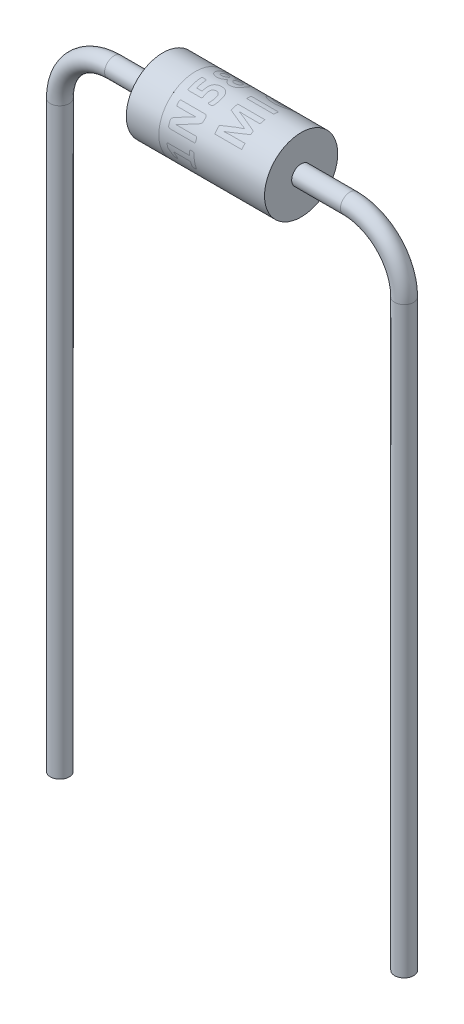
SolidWorks part; units mm, degrees
other "Diode"
other "Cathode Silver Band"
other "Wire"
ref_plane "Front Plane" through (0, 0, 0) normal (0, 0, 1) x (1, 0, 0)
ref_plane "Top Plane" through (0, 0, 0) normal (0, 1, 0) x (1, 0, 0)
ref_plane "Right Plane" through (0, 0, 0) normal (1, 0, 0) x (0, 0, -1)
sketch "Sketch1" plane through (0, 0, 0) normal (1, 0, 0) x (0, 0, -1)
  circle A0 centre (0, 0) radius 1.35
  circle A1 centre (0, 0) radius 0.35
  dimension "D1" = 2.7
  dimension "D2" = 0.7
extrude "Boss-Extrude1" add sketch "Sketch1" along normal mid plane 5.1
sketch "Sketch2" plane through (-2.55, 0, 0) normal (-1, 0, 0) x (0, 0, 1)
  circle A1 centre (0, 0) radius 1.35 construction
  circle A2 centre (0, 0) radius 1.34
  circle A3 centre (0, 0) radius 1.34
  circle A4 centre (0, 0) radius 1.35
  dimension "D1" = 0.01
extrude "Cut-Extrude1" cut sketch "Sketch2" against normal blind 1.2
sketch "Sketch3" plane through (-1.35, 0, 0) normal (-1, 0, 0) x (0, 0, 1)
  circle A0 centre (0, 0) radius 1.34 construction
  circle A1 centre (0, 0) radius 1.34
  circle A2 centre (0, 0) radius 1.35 construction
  circle A3 centre (0, 0) radius 1.35
extrude "Boss-Extrude2" add sketch "Sketch3" along normal up to surface (1.2 mm away) separate body up to face at (-2.55, 0, -0.35)
ref_plane "Plane1" through (0, 5, 0) normal (0, 1, 0) x (1, 0, 0)
sketch "Sketch4" plane through (0, 5, 0) normal (0, 1, 0) x (1, 0, 0)
  line L0 (-0.05, 7.5) -> (-0.05, -7.5) construction
  line L1 (-0.05, 0) -> (-2.55, 0) construction
  line L2 (-2.55, 1.35) -> (-2.55, -1.35) construction
  line L4 (-0.05, 0) -> (1.45, 0) construction
  line L5 (1.45, 7.5) -> (1.45, -7.5) construction
  text T0 "1N5817" font "Calibri" height 1
  text T1 "MIC" font "Corbel" height 1
  dimension "D1" = 2.5
  dimension "D2" = 15
  dimension "D3" = 1.5
wrap "Wrap1" sketch "Sketch4" wrap type scribe source sketch "Sketch4" face at (2.55, 0, -1.35)
sketch "Sketch5" plane through (0, 0, 0) normal (0, 0, 1) x (1, 0, 0)
  line L0 (0, 0) -> (-4.35, 0)
  line L1 (-6.35, -2) -> (-6.35, -23.5084)
  line L2 (0, 0) -> (4.35, 0)
  line L3 (6.35, -2) -> (6.35, -23.5084)
  arc A0 (-4.35, 0) -> (-6.35, -2) centre (-4.35, -2) ccw
  arc A1 (4.35, 0) -> (6.35, -2) centre (4.35, -2) cw
  dimension "D2" = 2
  dimension "D3" = 58
  dimension "D1" = 12.7
sketch "Sketch6" plane through (0, 0, 0) normal (1, 0, 0) x (0, 0, -1)
  circle A0 centre (0, 0) radius 0.35
  dimension "D1" = 0.7
sweep "Sweep1" add profiles "Sketch6" path "Sketch5"
